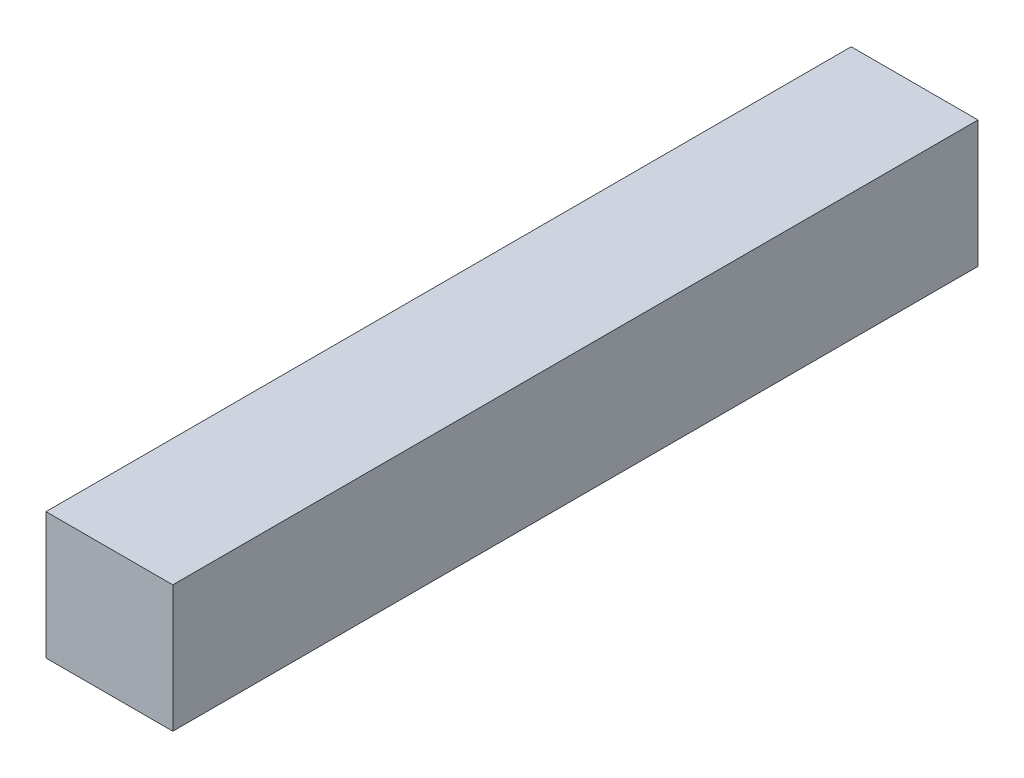
SolidWorks part; units mm, degrees
ref_plane "Front Plane" through (0, 0, 0) normal (0, 0, 1) x (1, 0, 0)
ref_plane "Top Plane" through (0, 0, 0) normal (0, 1, 0) x (1, 0, 0)
ref_plane "Right Plane" through (0, 0, 0) normal (1, 0, 0) x (0, 0, -1)
sketch "Sketch1" plane through (0, 0, 0) normal (0, 0, 1) x (1, 0, 0)
  line L1 (-1, 1) -> (1, 1)
  line L2 (-1, 1) -> (-1, -1)
  line L3 (-1, -1) -> (1, -1)
  line L4 (1, 1) -> (1, -1)
  line L5 (-1, 1) -> (1, -1) construction
  line L6 (-1, -1) -> (1, 1) construction
  point P0 (0, 0)
  dimension "D1" = 2
  dimension "D2" = 2
extrude "Boss-Extrude1" add sketch "Sketch1" along normal blind 12.7 contours L4 L3 L2 L1
